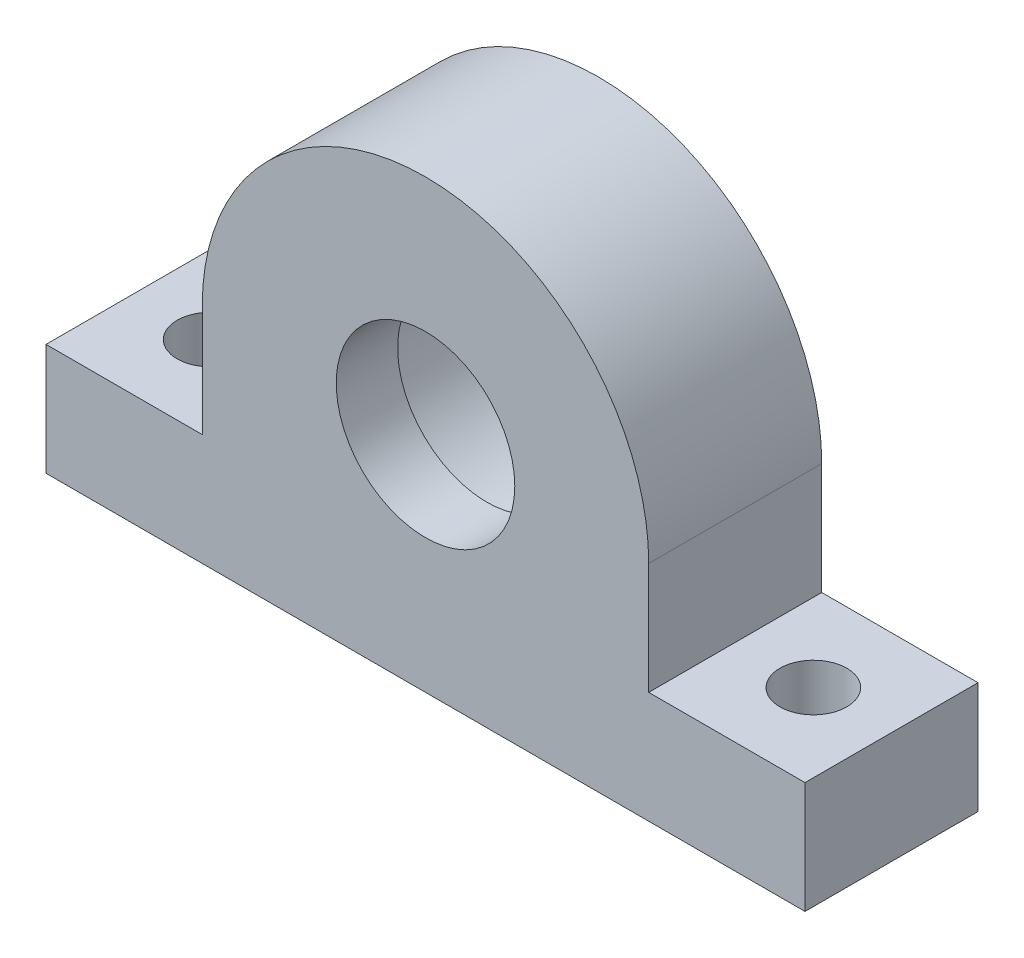
SolidWorks part; units mm, degrees
ref_plane "Front Plane" through (0, 0, 0) normal (0, 0, 1) x (1, 0, 0)
ref_plane "Top Plane" through (0, 0, 0) normal (0, 1, 0) x (1, 0, 0)
ref_plane "Right Plane" through (0, 0, 0) normal (1, 0, 0) x (0, 0, -1)
sketch "Sketch1" plane through (0, 0, 0) normal (0, 0, 1) x (1, 0, 0)
  line L0 (-34, 0) -> (34, 0)
  line L1 (34, 0) -> (34, 10)
  line L2 (34, 10) -> (20, 10)
  line L3 (20, 10) -> (20, 20)
  line L4 (0, -55) -> (0, 55) construction
  line L5 (-20, 10) -> (-20, 20)
  line L6 (-34, 10) -> (-20, 10)
  line L7 (-34, 0) -> (-34, 10)
  arc A0 (20, 20) -> (-20, 20) centre (0, 20) ccw
  circle A1 centre (0, 20) radius 10.9
  point P16 (0, 0)
  dimension "D2" = 20
  dimension "D1" = 21.8
  dimension "10" = 10
  dimension "D3" = 34
  dimension "D4" = 20
extrude "Boss-Extrude1" add sketch "Sketch1" along normal blind 10
sketch "Sketch2" plane through (0, 0, 10) normal (0, 0, 1) x (1, 0, 0)
  line L7 (34, 0) -> (34, 10)
  line L8 (34, 10) -> (20, 10)
  line L9 (20, 10) -> (20, 20)
  line L10 (-20, 20) -> (-20, 10)
  line L11 (-20, 10) -> (-34, 10)
  line L12 (-34, 10) -> (-34, 0)
  line L13 (-34, 0) -> (34, 0)
  line L14 (34, 0) -> (34, 10)
  line L15 (34, 10) -> (20, 10)
  line L16 (20, 10) -> (20, 20)
  line L17 (-20, 20) -> (-20, 10)
  line L18 (-20, 10) -> (-34, 10)
  line L19 (-34, 10) -> (-34, 0)
  line L20 (-34, 0) -> (34, 0)
  circle A0 centre (0, 20) radius 8
  arc A1 (20, 20) -> (-20, 20) centre (0, 20) ccw
  arc A2 (20, 20) -> (-20, 20) centre (0, 20) ccw
  dimension "D2" = 16
  dimension "D1" = 0
extrude "Boss-Extrude2" add sketch "Sketch2" along normal blind 5.5
sketch "Sketch3" plane through (0, 10, 0) normal (0, 1, 0) x (1, 0, 0)
  line L0 (-20, -15.5) -> (-34, 0) construction
  line L1 (20, -15.5) -> (34, 0) construction
  circle A0 centre (27, -7.75) radius 3
  circle A1 centre (-27, -7.75) radius 3
  point P13 (-27, -7.75)
  point P15 (27, -7.75)
  dimension "D1" = 6
  dimension "D2" = 6
extrude "Cut-Extrude1" cut sketch "Sketch3" against normal through all
